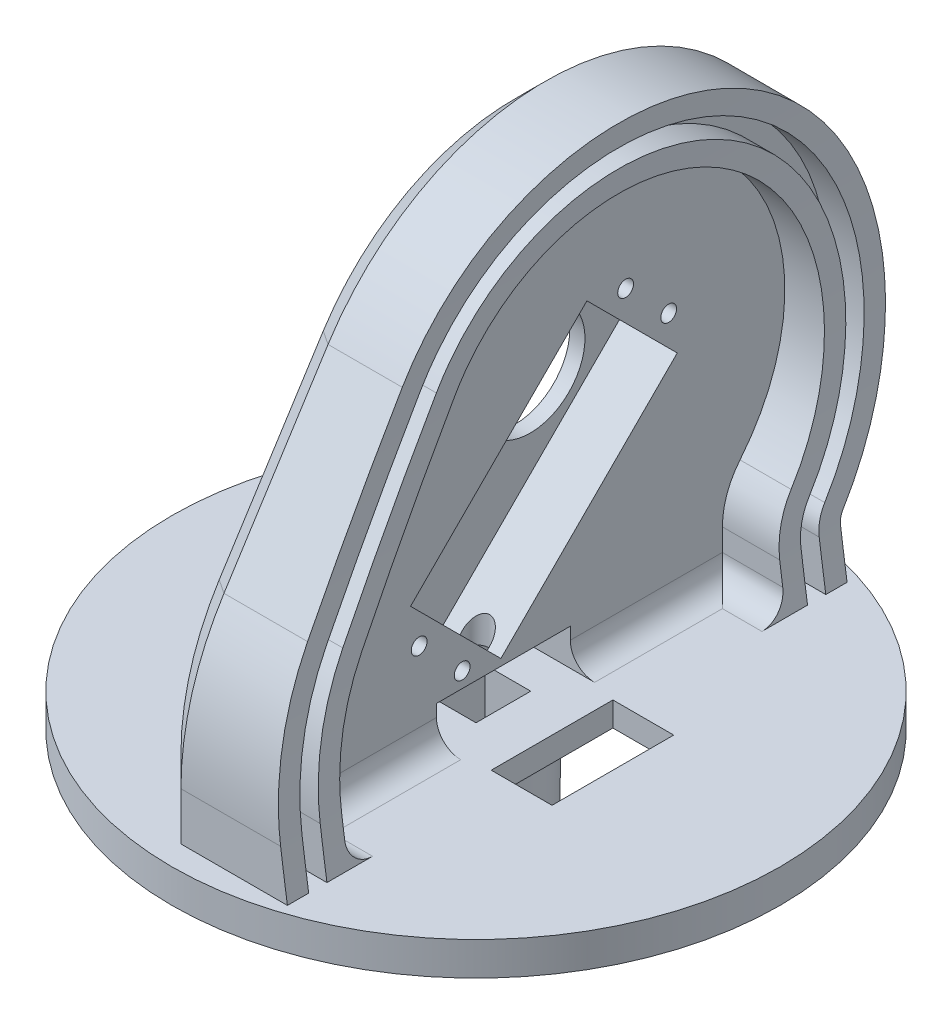
SolidWorks part; units mm, degrees
material "PLA"
ref_plane "Front Plane" through (0, 0, 0) normal (0, 0, 1) x (1, 0, 0)
ref_plane "Top Plane" through (0, 0, 0) normal (0, 1, 0) x (1, 0, 0)
ref_plane "Right Plane" through (0, 0, 0) normal (1, 0, 0) x (0, 0, -1)
sketch "Sketch1" plane through (0, 0, 0) normal (0, 1, 0) x (1, 0, 0)
  circle A0 centre (0, 0) radius 50
  dimension "D2" = 100
extrude "Boss-Extrude1" add sketch "Sketch1" along normal blind 4
sketch "Sketch2" plane through (0, 4, 0) normal (0, 1, 0) x (1, 0, 0)
  circle A0 centre (0, 0) radius 2.95
  dimension "D1" = 5.9
extrude "Cut-Extrude1" cut sketch "Sketch2" against normal blind 21.5
sketch "Sketch3" plane through (0, 0, 0) normal (1, 0, 0) x (0, 0, -1)
  line L0 (-36, 4) -> (36, 4)
  line L2 (36, 4) -> (36, 11.64)
  line L3 (50, 4) -> (-50, 4) construction
  line L4 (-36, 4) -> (-36, 11.86)
  line L5 (-13.3876, 57.6518) -> (-30.4919, 30.7746)
  arc A0 (36, 11.64) -> (38.8979, 19.7241) centre (48.725, 11.64) cw
  arc A1 (38.8979, 19.7241) -> (-13.3876, 57.6518) centre (13.91, 40.28) ccw
  arc A2 (-36, 11.86) -> (-30.4919, 30.7746) centre (-0.77, 11.86) cw
  circle A3 centre (13.91, 40.28) radius 9
  point P5 (0, 4)
  dimension "D5" = 35.23
  dimension "D6" = 18
  dimension "D1" = 72
  dimension "D2" = 7.64
  dimension "D4" = 7.86
  dimension "D7" = 13.91
  dimension "D8" = 40.28
extrude "Boss-Extrude2" add sketch "Sketch3" along normal blind 14 from offset 7.5 offset against normal yes
sketch "Sketch4" plane through (0, 0, 0) normal (1, 0, 0) x (0, 0, -1)
  line L0 (-0.41, 11.11) -> (28.5814, 40.1014)
  line L1 (-0.41, 11.11) -> (-15.2592, 25.9592)
  line L2 (28.5814, 40.1014) -> (13.7321, 54.9506)
  line L3 (-15.2592, 25.9592) -> (13.7321, 54.9506)
  line L5 (-36, 4) -> (36, 4) construction
  line L6 (-0.7636, 40.4549) -> (14.0857, 25.6057) construction
  line L7 (6.6611, 33.0303) -> (23.6316, 50.0009) construction
  line L8 (20.0961, 53.5364) -> (27.1672, 46.4653) construction
  circle A0 centre (20.0961, 53.5364) radius 1.3
  circle A1 centre (27.1672, 46.4653) radius 1.3
  circle A2 centre (-6.774, 12.5242) radius 1.3
  circle A3 centre (-13.845, 19.5953) radius 1.3
  point P12 (-0.7636, 40.4549)
  point P15 (23.6316, 50.0009)
  dimension "D6" = 3.5
  dimension "D8" = 2.6
  dimension "D1" = 0.41
  dimension "D2" = 11.11
  dimension "D3" = 21
  dimension "D4" = 41
  dimension "D5" = 45
  dimension "D7" = 10
extrude "Cut-Extrude2" cut sketch "Sketch4" along normal through all and the other way blind 5
sketch "Sketch5" plane through (6.5, 0, 0) normal (1, 0, 0) x (0, 0, -1)
  line L19 (-46, 4) -> (-36, 4)
  line L22 (-46, 11.86) -> (-46, 4)
  line L23 (-21.8241, 63.0207) -> (-38.9284, 36.1435)
  line L24 (46, 4) -> (46, 11.64)
  line L25 (-46, 11.86) -> (-46, 4)
  line L26 (-21.8241, 63.0207) -> (-38.9284, 36.1435)
  line L27 (46, 4) -> (46, 11.64)
  line L28 (36, 4) -> (36, 11.64) construction
  line L29 (-13.3876, 57.6518) -> (-30.4919, 30.7746) construction
  line L30 (-36, 11.86) -> (-36, 4) construction
  line L31 (36, 4) -> (36, 11.64)
  line L32 (-13.3876, 57.6518) -> (-30.4919, 30.7746)
  line L33 (-36, 11.86) -> (-36, 4)
  line L34 (36, 4) -> (46, 4)
  line L35 (46, 4) -> (46, 11.64)
  line L36 (-21.8241, 63.0207) -> (-38.9284, 36.1435)
  line L37 (-46, 11.86) -> (-46, 4)
  arc A18 (38.8979, 19.7241) -> (36, 11.64) centre (48.725, 11.64) ccw construction
  arc A19 (38.8979, 19.7241) -> (-13.3876, 57.6518) centre (13.91, 40.28) ccw construction
  arc A20 (-30.4919, 30.7746) -> (-36, 11.86) centre (-0.77, 11.86) ccw construction
  arc A21 (-38.9284, 36.1435) -> (-46, 11.86) centre (-0.77, 11.86) ccw
  arc A22 (46.6206, 13.3712) -> (-21.8241, 63.0207) centre (13.91, 40.28) ccw
  arc A23 (46.6206, 13.3712) -> (46, 11.64) centre (48.725, 11.64) ccw
  arc A24 (-38.9284, 36.1435) -> (-46, 11.86) centre (-0.77, 11.86) ccw
  arc A25 (46.6206, 13.3712) -> (-21.8241, 63.0207) centre (13.91, 40.28) ccw
  arc A26 (46.6206, 13.3712) -> (46, 11.64) centre (48.725, 11.64) ccw
  arc A27 (38.8979, 19.7241) -> (36, 11.64) centre (48.725, 11.64) ccw
  arc A28 (38.8979, 19.7241) -> (-13.3876, 57.6518) centre (13.91, 40.28) ccw
  arc A29 (-30.4919, 30.7746) -> (-36, 11.86) centre (-0.77, 11.86) ccw
  arc A30 (46.6206, 13.3712) -> (46, 11.64) centre (48.725, 11.64) ccw
  arc A31 (46.6206, 13.3712) -> (-21.8241, 63.0207) centre (13.91, 40.28) ccw
  arc A32 (-38.9284, 36.1435) -> (-46, 11.86) centre (-0.77, 11.86) ccw
  dimension "D1" = 10
  dimension "D2" = 10
extrude "Boss-Extrude3" add sketch "Sketch5" along normal blind 9 and the other way up to surface (14 mm away) other way up to face at (-7.5, 24.0112, -1.8744)
sketch "Sketch6" plane through (0, 0, 0) normal (0, 0, 1) x (1, 0, 0)
  line L6 (15.5, 4) -> (15, 4)
  line L8 (15.5, 82.6364) -> (-7.5, 82.6364) construction
  line L9 (9.5, 82.6364) -> (15.5, 82.6364)
  line L10 (15.5, 82.6364) -> (15.5, 4)
  arc A1 (15, 4) -> (9.5, 82.6364) centre (509.4794, 78.0955) cw
  dimension "D3" = 6
  dimension "D2" = 500
  dimension "D1" = 0.5
extrude "Cut-Extrude3" cut sketch "Sketch6" against normal through all both and the other way through all
chamfer "Chamfer1" distance 5 angle 45 6 edges at (-7.5, 7.93, 46) (-7.5, 7.82, -46) (-7.5, 24.5061, 44.1961) (-7.5, 12.5595, -46.1598) (-7.5, 49.5821, 30.3763) (-7.5, 74.5657, -38.7808)
sketch "Sketch8" plane through (0, 0, 0) normal (1, 0, 0) x (0, 0, -1)
  line L10 (-42.5, 4) -> (-42.5, 11.86)
  line L11 (-35.9756, 34.2644) -> (-18.8713, 61.1416)
  line L12 (42.5, 11.64) -> (42.5, 4)
  line L22 (39.5, 11.64) -> (39.5, 4)
  line L23 (-33.4447, 32.6537) -> (-16.3404, 59.5309)
  line L24 (-39.5, 4) -> (-39.5, 11.86)
  line L25 (39.5, 11.64) -> (39.5, 4)
  line L26 (-33.4447, 32.6537) -> (-16.3404, 59.5309)
  line L27 (-39.5, 4) -> (-39.5, 11.86)
  line L28 (-42.5, 4) -> (-39.5, 4)
  line L29 (39.5, 4) -> (42.5, 4)
  arc A13 (-35.9756, 34.2644) -> (-42.5, 11.86) centre (-0.77, 11.86) ccw
  arc A14 (43.9176, 15.5947) -> (-18.8713, 61.1416) centre (13.91, 40.28) ccw
  arc A15 (43.9176, 15.5947) -> (42.5, 11.64) centre (48.725, 11.64) ccw
  arc A16 (41.6008, 17.5006) -> (39.5, 11.64) centre (48.725, 11.64) ccw
  arc A17 (41.6008, 17.5006) -> (-16.3404, 59.5309) centre (13.91, 40.28) ccw
  arc A18 (-33.4447, 32.6537) -> (-39.5, 11.86) centre (-0.77, 11.86) ccw
  arc A19 (41.6008, 17.5006) -> (39.5, 11.64) centre (48.725, 11.64) ccw
  arc A20 (41.6008, 17.5006) -> (-16.3404, 59.5309) centre (13.91, 40.28) ccw
  arc A21 (-33.4447, 32.6537) -> (-39.5, 11.86) centre (-0.77, 11.86) ccw
  dimension "D1" = 3.5
  dimension "D2" = 3
extrude "Cut-Extrude4" cut sketch "Sketch8" along normal blind 12 from offset 5
sketch "Sketch11" plane through (6.5, 0, 0) normal (1, 0, 0) x (0, 0, -1)
  line L4 (36, 4) -> (36, 11.64)
  line L5 (-13.3876, 57.6518) -> (-30.4919, 30.7746)
  line L6 (-36, 11.86) -> (-36, 4)
  line L7 (-36, 4) -> (36, 4)
  line L8 (36, 4) -> (36, 11.64)
  line L9 (-13.3876, 57.6518) -> (-30.4919, 30.7746)
  line L10 (-36, 11.86) -> (-36, 4)
  line L11 (-36, 4) -> (36, 4)
  arc A3 (38.8979, 19.7241) -> (36, 11.64) centre (48.725, 11.64) ccw
  arc A4 (38.8979, 19.7241) -> (-13.3876, 57.6518) centre (13.91, 40.28) ccw
  arc A5 (-30.4919, 30.7746) -> (-36, 11.86) centre (-0.77, 11.86) ccw
  arc A6 (38.8979, 19.7241) -> (36, 11.64) centre (48.725, 11.64) ccw
  arc A7 (38.8979, 19.7241) -> (-13.3876, 57.6518) centre (13.91, 40.28) ccw
  arc A8 (-30.4919, 30.7746) -> (-36, 11.86) centre (-0.77, 11.86) ccw
  circle M8 centre (-13.845, 19.5953) radius 1.3
  circle M9 centre (-6.774, 12.5242) radius 1.3
  circle M10 centre (27.1672, 46.4653) radius 1.3
  circle M11 centre (20.0961, 53.5364) radius 1.3
  line M12 (28.5814, 40.1014) -> (-0.41, 11.11)
  line M13 (-0.41, 11.11) -> (-15.2592, 25.9592)
  line M14 (-15.2592, 25.9592) -> (13.7321, 54.9506)
  line M15 (13.7321, 54.9506) -> (28.5814, 40.1014)
  line M16 (36, 4) -> (36, 11.64)
  arc M17 (36, 11.64) -> (38.8979, 19.7241) centre (48.725, 11.64) cw
  arc M18 (38.8979, 19.7241) -> (-13.3876, 57.6518) centre (13.91, 40.28) ccw
  line M19 (-13.3876, 57.6518) -> (-30.4919, 30.7746)
  arc M20 (-30.4919, 30.7746) -> (-36, 11.86) centre (-0.77, 11.86) ccw
  line M21 (-36, 11.86) -> (-36, 4)
  line M22 (-36, 4) -> (36, 4)
  dimension "D1" = 0
extrude "Cut-Extrude9" cut sketch "Sketch11" against normal blind 3 from offset 1 contours M22 M16 M17 M18 M19 M20 M21 M9 M11 M15 M12 M13 M14 M10 M8
sketch "Sketch12" plane through (4.5, 0, 0) normal (1, 0, 0) x (0, 0, -1)
  line L0 (-11, 4) -> (11, 4)
  line L1 (50, 4) -> (-50, 4) construction
  line L2 (-11, 4) -> (-11, 9)
  line L3 (-11, 9) -> (11, 9)
  line L4 (11, 9) -> (11, 4)
  point P5 (0, 4)
  dimension "D1" = 22
  dimension "D2" = 5
  dimension "D3" = 4
extrude "Cut-Extrude10" cut sketch "Sketch12" against normal blind 7.5
chamfer "Chamfer2" distance 1 angle 45 1 edges at (4.5, 9, 0)
sketch "Sketch13" plane through (0, 0, 0) normal (0, -1, 0) x (1, 0, 0)
  line L0 (0, 7.5) -> (0, -7.5) construction
  line L1 (-7.5, 0) -> (7.5, 0) construction
  circle A0 centre (0, 0) radius 9.8
  circle A1 centre (7.5, 0) radius 1.05
  circle A2 centre (0, 0) radius 50
  circle A3 centre (0, 0) radius 50
  circle A4 centre (0, 0) radius 2.95 construction
  circle A5 centre (-7.5, 0) radius 1.05
  circle A6 centre (0, -7.25) radius 1.05
  circle A7 centre (0, 0) radius 2.95
  circle A8 centre (0, 7.5) radius 1.05
  point P4 (0, 0)
  point P17 (0, 0)
  point P18 (0, 0)
  dimension "D1" = 19.6
  dimension "D5" = 2.1
  dimension "D3" = 15
  dimension "D4" = 15
  dimension "D2" = 0
extrude "Boss-Extrude4" add sketch "Sketch13" along normal blind 18.5
fillet "Fillet1" radius 1.5 1 edges at (0, 0, 9.8)
sketch "Sketch14" plane through (0, 4, 0) normal (0, 1, 0) x (1, 0, 0)
  line L0 (-3, 11) -> (4.5, 11)
  line L1 (4.5, 11) -> (4.5, -11)
  line L2 (4.5, -11) -> (-3, -11)
  line L3 (-3, -11) -> (-3, 11)
  line L4 (-3, 4.5) -> (4.5, 4.5)
  line L5 (-45.45, 0) -> (45.45, 0) construction
  line L6 (-3, -4.5) -> (4.5, -4.5)
  circle M28 centre (0, 0) radius 2.95
  dimension "D1" = 4.5
extrude "Cut-Extrude12" cut sketch "Sketch14" against normal blind 15 contours L3 L6 L1 L4 M28
sketch "Sketch15" plane through (0, -18.5, 0) normal (0, -1, 0) x (1, 0, 0)
  circle A0 centre (0, 0) radius 2.95
  circle A1 centre (0, 0) radius 1.65
  dimension "D1" = 3.3
  dimension "D2" = 5.9
extrude "Boss-Extrude5" add sketch "Sketch15" against normal blind 5
sketch "Sketch16" plane through (0, 0, 0) normal (0, -1, 0) x (1, 0, 0)
  circle A0 centre (0, 0) radius 48
  circle A1 centre (0, 0) radius 50
  circle A2 centre (0, 0) radius 50
  dimension "D1" = 0
  dimension "D2" = 2
extrude "Boss-Extrude6" add sketch "Sketch16" along normal blind 1.5
chamfer "Chamfer3" distance 1.5 angle 45 1 edges at (0, -1.5, -48)
ref_plane "Plane1" through (0, 14, 0) normal (0, 1, 0) x (1, 0, 0)
sketch "Sketch17" plane through (0, 14, 0) normal (0, 1, 0) x (1, 0, 0)
  line L1 (12.5, 10) -> (22.5, 10)
  line L2 (12.5, 10) -> (12.5, -10)
  line L3 (12.5, -10) -> (22.5, -10)
  line L4 (22.5, 10) -> (22.5, -10)
  line L5 (12.5, 10) -> (22.5, -10) construction
  line L6 (12.5, -10) -> (22.5, 10) construction
  circle A0 centre (0, 0) radius 2.25
  point P3 (17.5, 0)
  dimension "D1" = 4.5
  dimension "D2" = 17.5
  dimension "D3" = 10
  dimension "D4" = 20
extrude "Cut-Extrude13" cut sketch "Sketch17" against normal up to surface (14 mm away) up to face at (0, 0, 11.3)
fillet "Fillet2" radius 2.5 1 edges at (-7.5, 4, 0)
fillet "Fillet3" radius 4 4 edges at (4.5, 4, 23.5) (4.5, 4, -23.5) (9.75, 4, -36) (9.75, 4, 36)
